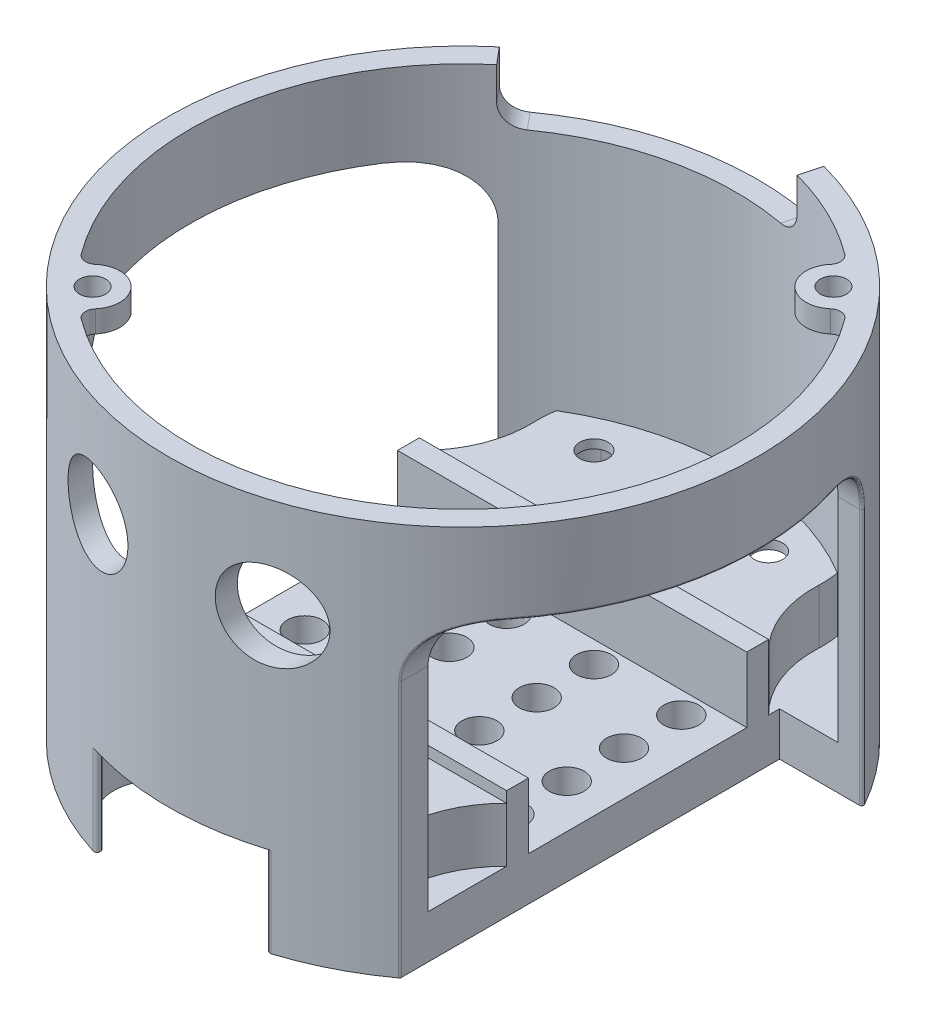
SolidWorks part; units mm, degrees
note: The reader was unsure of these and kept them because the rebuilt part matched: shared geometry of "草图1<2>", "草图8<3>", "草图14<3>".
ref_plane "前视基准面" through (0, 0, 0) normal (0, 0, 1) x (1, 0, 0)
ref_plane "上视基准面" through (0, 0, 0) normal (0, 1, 0) x (1, 0, 0)
ref_plane "右视基准面" through (0, 0, 0) normal (1, 0, 0) x (0, 0, -1)
sketch "草图1" plane through (0, 0, 0) normal (0, 1, 0) x (1, 0, 0)
  circle A0 centre (0, 0) radius 25
  circle A1 centre (0, 0) radius 27
  dimension "D1" = 2
  dimension "D2" = 50
extrude "凸台-拉伸1" add sketch "草图1" along normal blind 32
extrude "凸台-拉伸2" add sketch "草图1<2>" against normal blind 4 contours A0 | A1 A0
sketch "草图1<2>" plane through (0, 0, 0) normal (0, 1, 0) x (1, 0, 0) same geometry as "草图1"
sketch "草图2" plane through (0, -4, 0) normal (0, -1, 0) x (-1, 0, 0)
  line L0 (0, 0) -> (-38.3569, 0) construction
  line L1 (0, 0) -> (0, -28.1666) construction
  line L2 (-16, -5) -> (-32, -5) construction
  line L3 (-16, -23) -> (-32, -23)
  line L4 (-16, -23) -> (-16, 13)
  line L5 (-16, 13) -> (-32, 13)
  line L6 (-32, -23) -> (-32, 13)
  line L7 (-24, -5) -> (-24, -23) construction
  line L8 (16, 23) -> (16, -13)
  line L9 (16, 23) -> (32, 23)
  line L10 (32, 23) -> (32, -13)
  line L11 (16, -13) -> (32, -13)
  dimension "D1" = 16
  dimension "D2" = 5
  dimension "D3" = 36
  dimension "D4" = 2
  dimension "8" = 16
extrude "切除-拉伸1" cut sketch "草图2" against normal blind 28.5
sketch "草图3" plane through (0, 0, 0) normal (0, 1, 0) x (1, 0, 0)
  line L0 (0, 0) -> (0, -41.6569) construction
  line L1 (0, 0) -> (39.2154, 0) construction
  line L2 (0, -20) -> (35.8438, -20) construction
  line L3 (-9.875, -17.6581) -> (-5, -13.755)
  line L4 (-9.875, -22.3419) -> (-5, -26.245)
  line L5 (9.875, -22.3419) -> (5, -26.245)
  line L6 (16, -19.2094) -> (16, 13)
  line L7 (16, 13) -> (21.3542, 13)
  line L9 (-16, 19.2094) -> (-16, -13)
  line L10 (-16, -13) -> (-21.3542, -13)
  line L12 (16, -19.2094) -> (16, 13)
  line L13 (16, 13) -> (21.3542, 13)
  line L15 (-16, 19.2094) -> (-16, -13)
  line L16 (-16, -13) -> (-21.3542, -13)
  line L18 (9.875, -17.6581) -> (5, -13.755)
  circle A0 centre (0, 0) radius 25 construction
  arc A1 (0, -25) -> (-8.3467, -23.5655) centre (0, 0) ccw
  circle A2 centre (0, -20) radius 8
  circle A3 centre (8, -20) radius 3
  circle A4 centre (-8, -20) radius 3
  arc A6 (21.3542, 13) -> (-16, 19.2094) centre (0, 0) ccw
  arc A7 (21.3542, 13) -> (-16, 19.2094) centre (0, 0) ccw
  arc A8 (-21.3542, -13) -> (16, -19.2094) centre (0, 0) ccw
  arc A9 (-21.3542, -13) -> (16, -19.2094) centre (0, 0) ccw
  arc M32 (-21.3542, -13) -> (16, -19.2094) centre (0, 0) ccw
  dimension "D2" = 16
  dimension "D3" = 8
  dimension "D4" = 20
  dimension "D1" = 0
extrude "切除-拉伸2" cut sketch "草图3" against normal blind 5 and the other way blind 4 contours A4 A2 A1 A3 | A2 A4 | A4 A2 L3 | A2 A4 | A2 A3 | A3 A2 | A3 L18 A2 | A3 A2 L5 M32 | A4 L4 A2 M32 | A2 A1 | A2 L4 M32 | A2 L5 A1
mirror "镜向8" about plane through (0, 0, 0) normal (0, 0, 1) of "切除-拉伸2"
ref_plane "基准面1" through (0, 4, 0) normal (0, 1, 0) x (1, 0, 0)
sketch "草图7" plane through (0, 0, 0) normal (0, 1, 0) x (1, 0, 0)
  line L0 (-9.875, -22.3419) -> (-5, -26.245) construction
  line L1 (9.875, -17.6581) -> (5, -13.755) construction
  line L2 (9.875, -22.3419) -> (5, -26.245) construction
  line L3 (-9.875, -17.6581) -> (-5, -13.755) construction
  line L4 (-9.875, -22.3419) -> (-5, -26.245)
  line L5 (9.875, -17.6581) -> (5, -13.755)
  line L6 (-16, 19.2094) -> (-16, -13)
  line L8 (16, 13) -> (21.3542, 13)
  line L9 (16, -19.2094) -> (16, 13)
  line L11 (-16, -13) -> (-21.3542, -13)
  line L12 (-16, 19.2094) -> (-16, -13)
  line L14 (16, 13) -> (21.3542, 13)
  line L15 (16, -19.2094) -> (16, 13)
  line L17 (-16, -13) -> (-21.3542, -13)
  line L18 (9.875, -22.3419) -> (5, -26.245)
  line L19 (-9.875, -17.6581) -> (-5, -13.755)
  arc A0 (0, -25) -> (-8.3467, -23.5655) centre (0, 0) ccw construction
  circle A1 centre (-8, -20) radius 3
  circle A2 centre (-8, -20) radius 3
  circle A3 centre (8, -20) radius 3
  circle A4 centre (8, -20) radius 3
  circle A5 centre (0, -20) radius 8
  circle A6 centre (0, -20) radius 8
  arc A7 (0, -25) -> (-8.3467, -23.5655) centre (0, 0) ccw
  circle A8 centre (-8, -20) radius 1.3
  circle A9 centre (8, -20) radius 1.3
  arc A12 (-21.3542, -13) -> (16, -19.2094) centre (0, 0) ccw
  arc A13 (-21.3542, -13) -> (16, -19.2094) centre (0, 0) ccw
  arc A14 (21.3542, 13) -> (-16, 19.2094) centre (0, 0) ccw
  arc A15 (21.3542, 13) -> (-16, 19.2094) centre (0, 0) ccw
  ellipse E0 centre (0, -20) end of major axis (-13, -20) minor radius 10
  dimension "D1" = 0
  dimension "D2" = 0
  dimension "D3" = 0
  dimension "D4" = 0
sketch "草图8" plane through (0, 4, 0) normal (0, 1, 0) x (1, 0, 0)
  line L0 (9.875, -17.6581) -> (5, -13.755) construction
  line L1 (-9.875, -22.3419) -> (-5, -26.245) construction
  line L2 (-9.875, -17.6581) -> (-5, -13.755) construction
  line L3 (9.875, -22.3419) -> (5, -26.245) construction
  line L4 (9.875, -17.6581) -> (5, -13.755)
  line L5 (-9.875, -22.3419) -> (-5, -26.245)
  line L6 (-16, -13) -> (-21.3542, -13)
  line L8 (16, -19.2094) -> (16, 13)
  line L9 (16, 13) -> (21.3542, 13)
  line L11 (-16, 19.2094) -> (-16, -13)
  line L12 (-16, -13) -> (-21.3542, -13)
  line L14 (16, -19.2094) -> (16, 13)
  line L15 (16, 13) -> (21.3542, 13)
  line L17 (-16, 19.2094) -> (-16, -13)
  line L18 (-9.875, -17.6581) -> (-5, -13.755)
  line L19 (9.875, -22.3419) -> (5, -26.245)
  arc A0 (0, -25) -> (-8.3467, -23.5655) centre (0, 0) ccw construction
  circle A1 centre (0, -20) radius 8
  circle A2 centre (0, -20) radius 8
  circle A3 centre (8, -20) radius 3
  circle A4 centre (8, -20) radius 3
  circle A5 centre (-8, -20) radius 3
  circle A6 centre (-8, -20) radius 3
  circle A7 centre (8, -20) radius 1.3
  circle A8 centre (8, -20) radius 1.3
  circle A9 centre (-8, -20) radius 1.3
  circle A10 centre (-8, -20) radius 1.3
  arc A11 (0, -25) -> (-8.3467, -23.5655) centre (0, 0) ccw
  arc A14 (21.3542, 13) -> (-16, 19.2094) centre (0, 0) ccw
  arc A15 (21.3542, 13) -> (-16, 19.2094) centre (0, 0) ccw
  arc A16 (-21.3542, -13) -> (16, -19.2094) centre (0, 0) ccw
  arc A17 (-21.3542, -13) -> (16, -19.2094) centre (0, 0) ccw
  ellipse E1 centre (0, -20) end of major axis (-13, -20) minor radius 10
  ellipse E2 centre (0, -20) end of major axis (-13, -20) minor radius 10
  dimension "D1" = 0
  dimension "D2" = 0
  dimension "D3" = 0
  dimension "D4" = 0
  dimension "D5" = 0
  dimension "D6" = 0
  dimension "D7" = 0
extrude "凸台-拉伸6" add sketch "草图8" along normal blind 1
extrude "凸台-拉伸7" add sketch "草图8<3>" against normal blind 4
sketch "草图8<3>" plane through (0, 4, 0) normal (0, 1, 0) x (1, 0, 0) same geometry as "草图8"
mirror "镜向9" about plane through (0, 0, 0) normal (0, 0, 1) of "凸台-拉伸7", "凸台-拉伸6"
sketch "草图9" plane through (0, 0, 0) normal (0, 1, 0) x (1, 0, 0)
  line L0 (0, 0) -> (33.8389, 0) construction
  line L1 (0, 0) -> (0, 20.6714) construction
  line L2 (-16, -13) -> (-16, 19.2094) construction
  line L3 (-16, 10) -> (16, 10)
  line L4 (-16, 10) -> (-16, 12)
  line L5 (-16, 12) -> (16, 12)
  line L6 (16, 10) -> (16, 12)
  line L7 (16, 13) -> (16, -19.2094) construction
  line L8 (-16, -12) -> (16, -12)
  line L9 (16, -10) -> (16, -12)
  line L10 (-16, -10) -> (16, -10)
  line L11 (-16, -10) -> (-16, -12)
  dimension "D1" = 10
  dimension "D2" = 2
extrude "凸台-拉伸8" add sketch "草图9" along normal blind 6
fillet "圆角3" radius 5 4 edges at (16, 24.5, 20.479) (22.5092, 24.5, -13) (-22.5092, 24.5, 13) (-16, 24.5, -20.479)
fillet "圆角4" radius 0.2 10 edges at (16, 7.75, 21.7486) (16.7499, 22.1338, 21.1764) (26.517, 24.5, 5.0841) (24.5445, 23.2994, -11.2503) (-16, 7.75, -21.7486) (-16.7499, 22.1338, -21.1764) (-26.517, 24.5, -5.0841) (-24.5445, 23.2994, 11.2503) (23.6643, 7.75, -13) (-23.6643, 7.75, 13)
sketch "草图11" plane through (0, 0, 0) normal (0, 1, 0) x (1, 0, 0)
  line L0 (0, 0) -> (16, 0) construction
  line L1 (16, 10) -> (16, -10) construction
  line L2 (0, 0) -> (0, 10) construction
  line L3 (-16, 10) -> (16, 10) construction
  circle A0 centre (12, 8) radius 1.6
  circle A1 centre (4, 8) radius 1.6
  circle A2 centre (-4, 8) radius 1.6
  circle A3 centre (-12, 8) radius 1.6
  circle A4 centre (4, 2.75) radius 1.6
  circle A5 centre (-4, 2.75) radius 1.6
  circle A6 centre (-12, 2.75) radius 1.6
  circle A7 centre (4, -2.5) radius 1.6
  circle A8 centre (-4, -2.5) radius 1.6
  circle A9 centre (-12, -2.5) radius 1.6
  circle A10 centre (4, -7.75) radius 1.6
  circle A11 centre (-4, -7.75) radius 1.6
  circle A12 centre (-12, -7.75) radius 1.6
  circle A13 centre (12, 2.75) radius 1.6
  circle A14 centre (12, -2.5) radius 1.6
  circle A15 centre (12, -7.75) radius 1.6
  dimension "D1" = 8
  dimension "D2" = 12
  dimension "D3" = 4
  dimension "D4" = 4
extrude "切除-拉伸3" cut sketch "草图11" against normal blind 7
sketch "草图12" plane through (0, 32, 0) normal (0, 1, 0) x (1, 0, 0)
  line L0 (0, 0) -> (0, 27) construction
  line L1 (0, 0) -> (27, 0) construction
  line L3 (0, 0) -> (6.9881, 26.08)
  line L4 (0, 0) -> (-17.3553, 20.6832)
  circle A0 centre (0, 0) radius 27 construction
  circle A1 centre (0, 0) radius 25 construction
  circle A2 centre (0, 0) radius 27
  circle A3 centre (0, 0) radius 27
  circle A4 centre (0, 0) radius 25
  dimension "D1" = 0
extrude "切除-拉伸4" cut sketch "草图12" against normal blind 5
ref_plane "基准面2" through (0, 14, 0) normal (0, -1, 0) x (-1, 0, 0)
sketch "草图13" plane through (0, 14, 0) normal (0, -1, 0) x (-1, 0, 0)
  line L0 (0, 0) -> (-37.1162, 0) construction
  line L1 (0, 0) -> (0, 32.9189) construction
  line L2 (-17.5, 16.5) -> (-18.7816, 16.5)
  line L3 (17.5, 20.5) -> (-17.5, 20.5)
  line L4 (17.5, 20.5) -> (17.5, -20.5)
  line L5 (17.5, -20.5) -> (-17.5, -20.5)
  line L6 (-17.5, 20.5) -> (-17.5, -20.5)
  line L7 (-11.5, 20.5) -> (-11.5, 22.198)
  line L8 (11.5, 20.5) -> (11.5, 22.198)
  line L10 (-11.5, -20.5) -> (-11.5, -22.198)
  line L12 (11.5, -20.5) -> (11.5, -22.198)
  line L13 (17.5, -16.5) -> (18.7816, -16.5)
  arc A0 (16.0697, 19.1511) -> (-6.4705, 24.1481) centre (0, 0) ccw construction
  arc A1 (-6.4705, 24.1481) -> (16.0697, 19.1511) centre (0, 0) ccw construction
  arc A2 (16.0697, 19.1511) -> (-6.4705, 24.1481) centre (0, 0) ccw
  arc A3 (-6.4705, 24.1481) -> (16.0697, 19.1511) centre (0, 0) ccw
  point P10 (-17.5, 0)
  point P11 (0, 20.5)
  dimension "D1" = 35
  dimension "D2" = 41
  dimension "D3" = 6
  dimension "D4" = 4
  dimension "D5" = 4
  dimension "D6" = 6
  dimension "D7" = 6
  dimension "D8" = 6
extrude "凸台-拉伸11" [suppressed] add sketch "草图13" against normal blind 10 contours L7 A3 L3 | L6 A3 L2 | L12 A3 L5 | L4 A3 L13 | L3 A2 L8 | L5 A3 L10
sketch "草图14" plane through (0, 32, 0) normal (0, 1, 0) x (1, 0, 0)
  line L0 (0, 0) -> (19.0919, 19.0919) construction
  line L1 (0, 0) -> (19.0919, -19.0919) construction
  line L2 (-16.0697, 19.1511) -> (-17.3553, 20.6832)
  line L3 (6.9881, 26.08) -> (6.4705, 24.1481)
  line L4 (-16.0697, 19.1511) -> (-17.3553, 20.6832)
  line L5 (6.9881, 26.08) -> (6.4705, 24.1481)
  line L6 (-17.3553, 20.6832) -> (-16.0697, 19.1511)
  line L7 (6.4705, 24.1481) -> (6.9881, 26.08)
  line L8 (-17.3553, 20.6832) -> (-16.0697, 19.1511)
  line L9 (6.4705, 24.1481) -> (6.9881, 26.08)
  circle A0 centre (16.9706, 16.9706) radius 1.2
  circle A1 centre (16.9706, 16.9706) radius 2.5
  arc A2 (-16.0697, 19.1511) -> (6.4705, 24.1481) centre (0, 0) ccw
  arc A3 (-17.3553, 20.6832) -> (6.9881, 26.08) centre (0, 0) ccw
  arc A4 (-16.0697, 19.1511) -> (6.4705, 24.1481) centre (0, 0) ccw
  arc A5 (-17.3553, 20.6832) -> (6.9881, 26.08) centre (0, 0) ccw
  arc A6 (6.4705, 24.1481) -> (-16.0697, 19.1511) centre (0, 0) ccw
  arc A7 (6.9881, 26.08) -> (-17.3553, 20.6832) centre (0, 0) ccw
  arc A8 (6.4705, 24.1481) -> (-16.0697, 19.1511) centre (0, 0) ccw
  arc A9 (6.9881, 26.08) -> (-17.3553, 20.6832) centre (0, 0) ccw
  circle A10 centre (-16.9706, -16.9706) radius 1.2
  circle A11 centre (-16.9706, -16.9706) radius 2.5
  arc M11 (6.4705, 24.1481) -> (-16.0697, 19.1511) centre (0, 0) cw
  dimension "D3" = 2.4
  dimension "D4" = 24
  dimension "D5" = 5
  dimension "D1" = 0
  dimension "D2" = 0
extrude "凸台-拉伸12" add sketch "草图14" against normal blind 2
fillet "圆角6" radius 1 4 edges at (15.9485, 31, -19.2521) (19.2521, 31, -15.9485) (-15.9485, 31, 19.2521) (-19.2521, 31, 15.9485)
sketch "草图15" plane through (0, -4, 0) normal (0, -1, 0) x (1, 0, 0)
  line L8 (10.5, 23.1225) -> (5.625, 27.0256)
  line L9 (-5.625, 27.0256) -> (-10.5, 23.1225)
  line L10 (-10.5, 16.8775) -> (-5.625, 12.9744)
  line L12 (16, -13) -> (16, 21.6472)
  line L13 (5, 26.245) -> (9.875, 22.3419)
  line L14 (5, 26.245) -> (9.875, 22.3419)
  line L15 (9.875, 17.6581) -> (5, 13.755)
  line L16 (9.875, 17.6581) -> (5, 13.755)
  line L17 (-23.3238, 13) -> (-16, 13)
  line L18 (-16, 13) -> (-16, -21.6472)
  line L19 (-5, 13.755) -> (-9.875, 17.6581)
  line L20 (-5, 13.755) -> (-9.875, 17.6581)
  line L21 (-9.875, 22.3419) -> (-5, 26.245)
  line L22 (-9.875, 22.3419) -> (-5, 26.245)
  line L23 (23.3238, -13) -> (16, -13)
  line L24 (16, -13) -> (16, 21.6472)
  line L29 (-23.3238, 13) -> (-16, 13)
  line L30 (-16, 13) -> (-16, -21.6472)
  line L35 (23.3238, -13) -> (16, -13)
  line L36 (10.5, 23.1225) -> (5.625, 27.0256)
  line L37 (-5.625, 27.0256) -> (-10.5, 23.1225)
  line L44 (-10.5, -23.1225) -> (-5.625, -27.0256)
  line L45 (5.625, -27.0256) -> (10.5, -23.1225)
  line L46 (10.5, -16.8775) -> (5.625, -12.9744)
  line L48 (-10.5, -23.1225) -> (-5.625, -27.0256)
  line L49 (5.625, -27.0256) -> (10.5, -23.1225)
  line L52 (-10.5, 16.8775) -> (-5.625, 12.9744)
  line L54 (10.5, -16.8775) -> (5.625, -12.9744)
  line L56 (5.625, 12.9744) -> (10.5, 16.8775)
  line L57 (5.625, 12.9744) -> (10.5, 16.8775)
  line L58 (-5.625, -12.9744) -> (-10.5, -16.8775)
  line L59 (-5.625, -12.9744) -> (-10.5, -16.8775)
  line L60 (-5, -26.245) -> (-9.875, -22.3419)
  line L61 (-5, -26.245) -> (-9.875, -22.3419)
  line L62 (-9.875, -17.6581) -> (-5, -13.755)
  line L63 (-9.875, -17.6581) -> (-5, -13.755)
  line L64 (5, -13.755) -> (9.875, -17.6581)
  line L65 (5, -13.755) -> (9.875, -17.6581)
  line L66 (9.875, -22.3419) -> (5, -26.245)
  line L67 (9.875, -22.3419) -> (5, -26.245)
  arc A12 (10.5, 16.8775) -> (10.5, 23.1225) centre (8, 20) ccw
  arc A13 (5.625, 27.0256) -> (4.86, 27.575) centre (0, 20) ccw
  arc A14 (4.86, 27.575) -> (-4.86, 27.575) centre (0, 0) ccw
  arc A15 (-4.86, 27.575) -> (-5.625, 27.0256) centre (0, 20) ccw
  arc A17 (10.5, 16.8775) -> (10.5, 23.1225) centre (8, 20) ccw
  arc A18 (16, 21.6472) -> (15.9179, 21.8087) centre (15.8, 21.6472) ccw
  arc A19 (15.9179, 21.8087) -> (4.4843, 26.625) centre (0, 0) ccw
  arc A20 (5, 26.245) -> (4.4843, 26.625) centre (0, 20) ccw
  arc A21 (5, 26.245) -> (4.4843, 26.625) centre (0, 20) ccw
  arc A22 (9.875, 17.6581) -> (9.875, 22.3419) centre (8, 20) ccw
  arc A23 (9.875, 17.6581) -> (9.875, 22.3419) centre (8, 20) ccw
  arc A24 (-5, 13.755) -> (5, 13.755) centre (0, 20) ccw
  arc A25 (-4.4843, 26.625) -> (-23.4979, 13.2985) centre (0, 0) ccw
  arc A26 (-23.4979, 13.2985) -> (-23.3238, 13) centre (-23.3238, 13.2) ccw
  arc A27 (-16, -21.6472) -> (-15.9179, -21.8087) centre (-15.8, -21.6472) ccw
  arc A28 (-15.9179, -21.8087) -> (-4.4843, -26.625) centre (0, 0) ccw
  arc A29 (-5, 13.755) -> (5, 13.755) centre (0, 20) ccw
  arc A30 (-9.875, 22.3419) -> (-9.875, 17.6581) centre (-8, 20) ccw
  arc A31 (-9.875, 22.3419) -> (-9.875, 17.6581) centre (-8, 20) ccw
  arc A32 (-4.4843, 26.625) -> (-5, 26.245) centre (0, 20) ccw
  arc A33 (-4.4843, 26.625) -> (-5, 26.245) centre (0, 20) ccw
  arc A34 (4.4843, -26.625) -> (23.4979, -13.2985) centre (0, 0) ccw
  arc A35 (23.4979, -13.2985) -> (23.3238, -13) centre (23.3238, -13.2) ccw
  arc A36 (16, 21.6472) -> (15.9179, 21.8087) centre (15.8, 21.6472) ccw
  arc A37 (15.9179, 21.8087) -> (4.4843, 26.625) centre (0, 0) ccw
  arc A43 (-4.4843, 26.625) -> (-23.4979, 13.2985) centre (0, 0) ccw
  arc A44 (-23.4979, 13.2985) -> (-23.3238, 13) centre (-23.3238, 13.2) ccw
  arc A45 (-16, -21.6472) -> (-15.9179, -21.8087) centre (-15.8, -21.6472) ccw
  arc A46 (-15.9179, -21.8087) -> (-4.4843, -26.625) centre (0, 0) ccw
  arc A52 (4.4843, -26.625) -> (23.4979, -13.2985) centre (0, 0) ccw
  arc A53 (23.4979, -13.2985) -> (23.3238, -13) centre (23.3238, -13.2) ccw
  arc A55 (5.625, 27.0256) -> (4.86, 27.575) centre (0, 20) ccw
  arc A56 (4.86, 27.575) -> (-4.86, 27.575) centre (0, 0) ccw
  arc A57 (-4.86, 27.575) -> (-5.625, 27.0256) centre (0, 20) ccw
  arc A66 (-10.5, -16.8775) -> (-10.5, -23.1225) centre (-8, -20) ccw
  arc A67 (-5.625, -27.0256) -> (-4.86, -27.575) centre (0, -20) ccw
  arc A68 (-4.86, -27.575) -> (4.86, -27.575) centre (0, 0) ccw
  arc A69 (4.86, -27.575) -> (5.625, -27.0256) centre (0, -20) ccw
  arc A71 (-10.5, -16.8775) -> (-10.5, -23.1225) centre (-8, -20) ccw
  arc A73 (-5.625, -27.0256) -> (-4.86, -27.575) centre (0, -20) ccw
  arc A74 (-4.86, -27.575) -> (4.86, -27.575) centre (0, 0) ccw
  arc A75 (4.86, -27.575) -> (5.625, -27.0256) centre (0, -20) ccw
  arc A78 (-5, -26.245) -> (-4.4843, -26.625) centre (0, -20) ccw
  arc A79 (-5, -26.245) -> (-4.4843, -26.625) centre (0, -20) ccw
  arc A80 (-9.875, -17.6581) -> (-9.875, -22.3419) centre (-8, -20) ccw
  arc A81 (-9.875, -17.6581) -> (-9.875, -22.3419) centre (-8, -20) ccw
  arc A83 (-10.5, 23.1225) -> (-10.5, 16.8775) centre (-8, 20) ccw
  arc A86 (10.5, -23.1225) -> (10.5, -16.8775) centre (8, -20) ccw
  arc A88 (-10.5, 23.1225) -> (-10.5, 16.8775) centre (-8, 20) ccw
  arc A89 (-5.625, 12.9744) -> (5.625, 12.9744) centre (0, 20) ccw
  arc A90 (-5.625, 12.9744) -> (5.625, 12.9744) centre (0, 20) ccw
  arc A91 (10.5, -23.1225) -> (10.5, -16.8775) centre (8, -20) ccw
  arc A92 (5.625, -12.9744) -> (-5.625, -12.9744) centre (0, -20) ccw
  arc A93 (5.625, -12.9744) -> (-5.625, -12.9744) centre (0, -20) ccw
  arc A94 (5, -13.755) -> (-5, -13.755) centre (0, -20) ccw
  arc A95 (5, -13.755) -> (-5, -13.755) centre (0, -20) ccw
  arc A96 (9.875, -22.3419) -> (9.875, -17.6581) centre (8, -20) ccw
  arc A97 (9.875, -22.3419) -> (9.875, -17.6581) centre (8, -20) ccw
  arc A98 (4.4843, -26.625) -> (5, -26.245) centre (0, -20) ccw
  arc A99 (4.4843, -26.625) -> (5, -26.245) centre (0, -20) ccw
  arc M69 (15.9179, 21.8087) -> (4.4843, 26.625) centre (0, 0) ccw
  arc M70 (4.4843, 26.625) -> (5, 26.245) centre (0, 20) cw
  line M71 (5, 26.245) -> (9.875, 22.3419)
  arc M72 (9.875, 22.3419) -> (9.875, 17.6581) centre (8, 20) cw
  line M73 (9.875, 17.6581) -> (5, 13.755)
  arc M74 (5, 13.755) -> (-5, 13.755) centre (0, 20) cw
  line M75 (-5, 13.755) -> (-9.875, 17.6581)
  arc M76 (-9.875, 17.6581) -> (-9.875, 22.3419) centre (-8, 20) cw
  line M77 (-9.875, 22.3419) -> (-5, 26.245)
  arc M78 (-5, 26.245) -> (-4.4843, 26.625) centre (0, 20) cw
  arc M79 (-4.4843, 26.625) -> (-23.4979, 13.2985) centre (0, 0) ccw
  arc M84 (-15.9179, -21.8087) -> (-4.4843, -26.625) centre (0, 0) ccw
  arc M85 (-4.4843, -26.625) -> (-5, -26.245) centre (0, -20) cw
  line M86 (-5, -26.245) -> (-9.875, -22.3419)
  arc M87 (-9.875, -22.3419) -> (-9.875, -17.6581) centre (-8, -20) cw
  line M88 (-9.875, -17.6581) -> (-5, -13.755)
  arc M89 (-5, -13.755) -> (5, -13.755) centre (0, -20) cw
  line M90 (5, -13.755) -> (9.875, -17.6581)
  arc M91 (9.875, -17.6581) -> (9.875, -22.3419) centre (8, -20) cw
  line M92 (9.875, -22.3419) -> (5, -26.245)
  arc M93 (5, -26.245) -> (4.4843, -26.625) centre (0, -20) cw
  arc M94 (4.4843, -26.625) -> (23.4979, -13.2985) centre (0, 0) ccw
  dimension "D1" = 0
  dimension "D2" = 1
  dimension "D3" = 1
extrude "切除-拉伸5" cut sketch "草图15" against normal blind 8 contours L52 A90 L57 A17 L36 L37 A88 M69 M70 M71 M72 M73 M74 M75 M76 M77 M78 M79 | L54 A93 L59 A71 L48 L49 A91 M84 M85 M86 M87 M88 M89 M90 M91 M92 M93 M94
fillet "圆角7" radius 0.3 4 edges at (-6.7173, 0, -26.151) (6.7173, 0, -26.151) (6.7173, 0, 26.151) (-6.7173, 0, 26.151)
ref_plane "基准面3" through (0, 6, 0) normal (0, 1, 0) x (1, 0, 0)
ref_point "点1"
extrude "切除-拉伸6" cut sketch "草图14<3>" against normal blind 8 contours A10 A4 | A0 M11
sketch "草图14<3>" plane through (0, 32, 0) normal (0, 1, 0) x (1, 0, 0) same geometry as "草图14"
fillet "圆角8" radius 10 4 edges at (-7.8, 2.5, 12) (7.8, 2.5, 12) (-7.8, 2.5, -12) (7.8, 2.5, -12)
sketch "草图16" plane through (0, 4, 0) normal (0, -1, 0) x (1, 0, 0)
  line L0 (10.5, 23.1225) -> (7.8848, 25.2163) construction
  line L1 (-7.8848, 25.2163) -> (-10.5, 23.1225) construction
  line L2 (-10.5, 16.8775) -> (-5.625, 12.9744) construction
  line L3 (5.625, 12.9744) -> (10.5, 16.8775) construction
  line L4 (-10.5, -23.1225) -> (-7.8848, -25.2163) construction
  line L5 (7.8848, -25.2163) -> (10.5, -23.1225) construction
  line L6 (10.5, -16.8775) -> (5.625, -12.9744) construction
  line L7 (-5.625, -12.9744) -> (-10.5, -16.8775) construction
  line L8 (10.5, 23.1225) -> (7.8848, 25.2163)
  line L9 (-7.8848, 25.2163) -> (-10.5, 23.1225)
  line L10 (-10.5, 16.8775) -> (-5.625, 12.9744)
  line L11 (5.625, 12.9744) -> (10.5, 16.8775)
  line L12 (-10.5, -23.1225) -> (-7.8848, -25.2163)
  line L13 (7.8848, -25.2163) -> (10.5, -23.1225)
  line L14 (10.5, -16.8775) -> (5.625, -12.9744)
  line L15 (-5.625, -12.9744) -> (-10.5, -16.8775)
  arc A0 (8.163, 25.7364) -> (7.8848, 25.2163) centre (8.0723, 25.4505) ccw construction
  arc A1 (8.163, 25.7364) -> (-8.163, 25.7364) centre (0, 0) ccw construction
  arc A2 (-7.8848, 25.2163) -> (-8.163, 25.7364) centre (-8.0723, 25.4505) ccw construction
  arc A3 (-10.5, 23.1225) -> (-10.5, 16.8775) centre (-8, 20) ccw construction
  arc A4 (-5.625, 12.9744) -> (5.625, 12.9744) centre (0, 20) ccw construction
  arc A5 (10.5, 16.8775) -> (10.5, 23.1225) centre (8, 20) ccw construction
  arc A6 (-8.163, -25.7364) -> (-7.8848, -25.2163) centre (-8.0723, -25.4505) ccw construction
  arc A7 (-8.163, -25.7364) -> (8.163, -25.7364) centre (0, 0) ccw construction
  arc A8 (7.8848, -25.2163) -> (8.163, -25.7364) centre (8.0723, -25.4505) ccw construction
  arc A9 (10.5, -23.1225) -> (10.5, -16.8775) centre (8, -20) ccw construction
  arc A10 (5.625, -12.9744) -> (-5.625, -12.9744) centre (0, -20) ccw construction
  arc A11 (-10.5, -16.8775) -> (-10.5, -23.1225) centre (-8, -20) ccw construction
  arc A12 (8.163, 25.7364) -> (7.8848, 25.2163) centre (8.0723, 25.4505) ccw
  arc A13 (8.163, 25.7364) -> (-8.163, 25.7364) centre (0, 0) ccw
  arc A14 (-7.8848, 25.2163) -> (-8.163, 25.7364) centre (-8.0723, 25.4505) ccw
  arc A15 (-10.5, 23.1225) -> (-10.5, 16.8775) centre (-8, 20) ccw
  arc A16 (-5.625, 12.9744) -> (5.625, 12.9744) centre (0, 20) ccw
  arc A17 (10.5, 16.8775) -> (10.5, 23.1225) centre (8, 20) ccw
  arc A18 (-8.163, -25.7364) -> (-7.8848, -25.2163) centre (-8.0723, -25.4505) ccw
  arc A19 (-8.163, -25.7364) -> (8.163, -25.7364) centre (0, 0) ccw
  arc A20 (7.8848, -25.2163) -> (8.163, -25.7364) centre (8.0723, -25.4505) ccw
  arc A21 (10.5, -23.1225) -> (10.5, -16.8775) centre (8, -20) ccw
  arc A22 (5.625, -12.9744) -> (-5.625, -12.9744) centre (0, -20) ccw
  arc A23 (-10.5, -16.8775) -> (-10.5, -23.1225) centre (-8, -20) ccw
extrude "切除-拉伸7" cut sketch "草图16" against normal blind 0.2
fillet "圆角9" radius 2 2 edges at (6.7293, 27, -25.1141) (-16.7125, 27, -19.9172)
sketch "草图17" plane through (0, 0, 0) normal (0, 0, 1) x (1, 0, 0)
  line L0 (0, 0) -> (0, 45.5545) construction
  line L1 (0, 22.7772) -> (37.4318, 22.7772) construction
  line L3 (-8, 12.2349) -> (8, 12.2349)
  line L4 (-8, 12.2349) -> (-8, 8.2349)
  line L5 (-8, 8.2349) -> (8, 8.2349)
  line L6 (8, 12.2349) -> (8, 8.2349)
  circle A0 centre (8, 22.7772) radius 4
  circle A1 centre (-8, 22.7772) radius 4
  arc A2 (-8, 12.2349) -> (8, 12.2349) centre (0, 18.2349) ccw
  point P13 (0, 12.2349)
  dimension "D1" = 8
  dimension "D2" = 16
  dimension "D3" = 4
extrude "切除-拉伸8" cut sketch "草图17" along normal blind 48 contours A1 | A0
fillet "圆角10" [suppressed] radius 0.5
